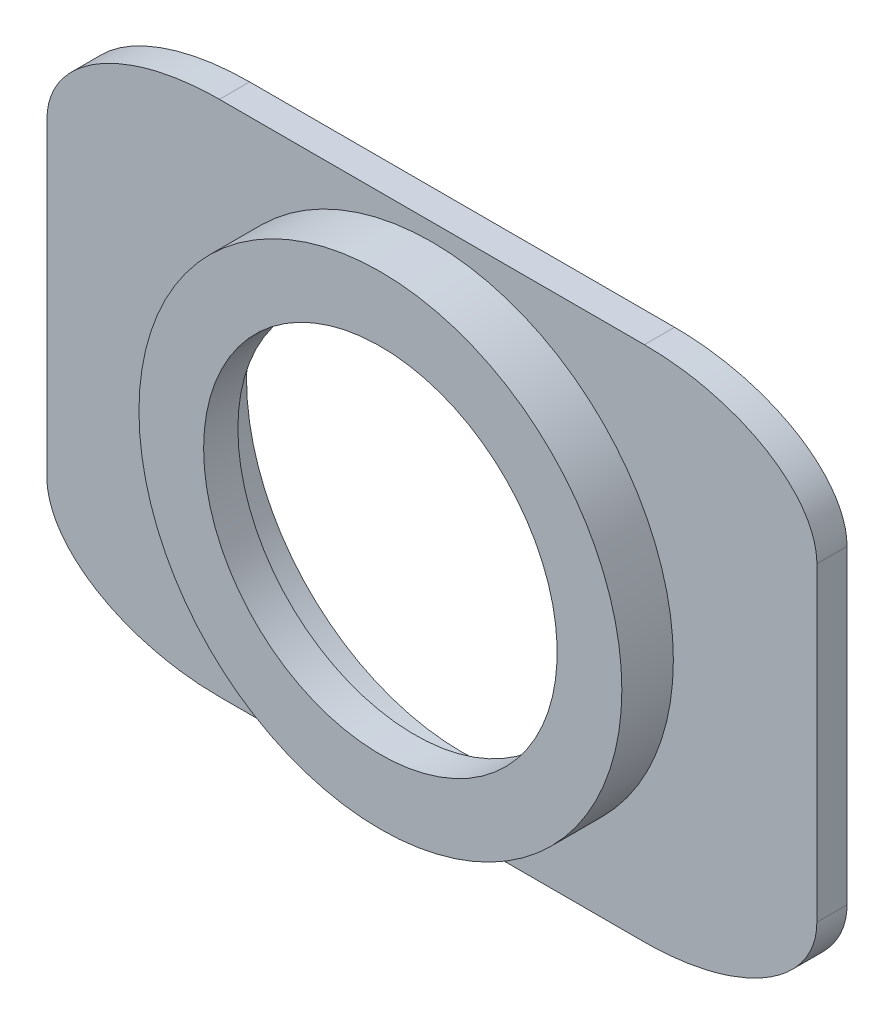
SolidWorks part; units mm, degrees
ref_plane "Front Plane" through (0, 0, 0) normal (0, 0, 1) x (1, 0, 0)
ref_plane "Top Plane" through (0, 0, 0) normal (0, 1, 0) x (1, 0, 0)
ref_plane "Right Plane" through (0, 0, 0) normal (1, 0, 0) x (0, 0, -1)
sketch "Sketch1" plane through (0, 0, 0) normal (0, 1, 0) x (1, 0, 0)
  line L0 (-44.6395, 1.8647) -> (-31.9395, 1.8647)
  line L1 (-31.9395, 1.8647) -> (-31.9395, -4.1087)
  line L2 (-31.9395, -4.1087) -> (31.9395, -4.1087)
  line L3 (31.9395, -4.1087) -> (31.9395, 1.8647)
  line L4 (31.9395, 1.8647) -> (44.6395, 1.8647)
  line L5 (44.6395, 1.8647) -> (44.6395, 5.3647)
  line L6 (44.6395, 5.3647) -> (-44.6395, 5.3647)
  line L7 (-44.6395, 5.3647) -> (-44.6395, 1.8647)
extrude "Boss-Extrude1" add sketch "Sketch1" along normal blind 60
sketch "Sketch2" plane through (0, 0, -5.3647) normal (0, 0, -1) x (-1, 0, 0)
  line L0 (0, 0) -> (0, 60) construction
  line L2 (-44.6395, 60) -> (44.6395, 60) construction
  circle A0 centre (0, 30) radius 25
extrude "Cut-Extrude1" cut sketch "Sketch2" against normal blind 5.5
fillet "Fillet1" radius 12 2 edges at (-44.6395, 60, -3.6147) (44.6395, 60, -3.6147) second distance 20 first distance on face at (-44.6395, 30, -3.6147) first distance on face at (44.6395, 30, -3.6147)
fillet "Fillet2" radius 12 1 edges at (44.6395, 0, -3.6147) second distance 20 first distance on face at (44.6395, 36, -4.0522)
fillet "Fillet3" radius 12 1 edges at (-44.6395, 0, -3.6147) second distance 20 first distance on face at (-44.6395, 36, -3.1772)
sketch "Sketch4" plane through (0, 0, 0.1353) normal (0, 0, -1) x (-1, 0, 0)
  circle A0 centre (0, 30) radius 20.5
extrude "Cut-Extrude2" cut sketch "Sketch4" against normal blind 8.5
sketch "Sketch6" plane through (0, 0, 4.1087) normal (0, 0, 1) x (1, 0, 0)
  line L8 (-31.9395, 59.1721) -> (-31.9395, 0.8279)
  line L9 (-24.6395, 0) -> (24.6395, 0)
  line L10 (31.9395, 0.8279) -> (31.9395, 59.1721)
  line L11 (24.6395, 60) -> (-24.6395, 60)
  line L12 (-31.9395, 59.1721) -> (-31.9395, 0.8279)
  line L13 (-24.6395, 0) -> (24.6395, 0)
  line L14 (31.9395, 0.8279) -> (31.9395, 59.1721)
  line L15 (24.6395, 60) -> (-24.6395, 60)
  circle A0 centre (0, 30) radius 28
  parabola Q8 (-31.9395, 0.8279) -> (-24.6395, 0) focus (-29.5867, 15.7036) apex (-34.0872, 1.4178)
  parabola Q9 (24.6395, 0) -> (31.9395, 0.8279) focus (29.5867, 15.7036) apex (34.0872, 1.4178)
  parabola Q10 (31.9395, 59.1721) -> (24.6395, 60) focus (29.5867, 44.2964) apex (34.0872, 58.5822)
  parabola Q11 (-24.6395, 60) -> (-31.9395, 59.1721) focus (-29.5867, 44.2964) apex (-34.0872, 58.5822)
  parabola Q12 (-31.9395, 0.8279) -> (-24.6395, 0) focus (-29.5867, 15.7036) apex (-34.0872, 1.4178)
  parabola Q13 (24.6395, 0) -> (31.9395, 0.8279) focus (29.5867, 15.7036) apex (34.0872, 1.4178)
  parabola Q14 (31.9395, 59.1721) -> (24.6395, 60) focus (29.5867, 44.2964) apex (34.0872, 58.5822)
  parabola Q15 (-24.6395, 60) -> (-31.9395, 59.1721) focus (-29.5867, 44.2964) apex (-34.0872, 58.5822)
  dimension "D2" = 56
  dimension "D1" = 0
extrude "Cut-Extrude3" cut sketch "Sketch6" against normal up to surface (5.9734 mm away) up to face at (-38.2895, 44.586, -1.8647)
